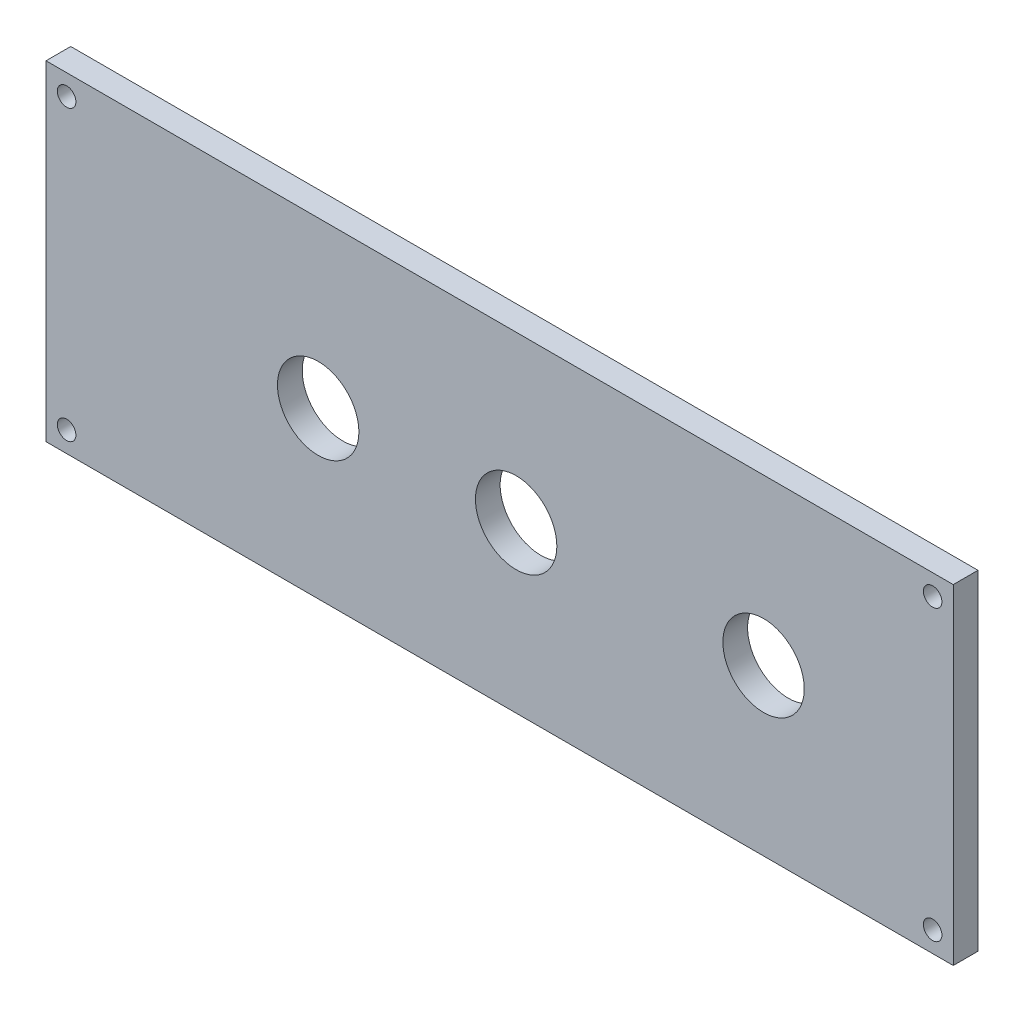
SolidWorks part; units mm, degrees
ref_plane "Front Plane" through (0, 0, 0) normal (0, 0, 1) x (1, 0, 0)
ref_plane "Top Plane" through (0, 0, 0) normal (0, 1, 0) x (1, 0, 0)
ref_plane "Right Plane" through (0, 0, 0) normal (1, 0, 0) x (0, 0, -1)
sketch "Sketch1" plane through (0, 0, 0) normal (0, 0, 1) x (1, 0, 0)
  line L1 (0, 0) -> (110, 0)
  line L2 (0, 0) -> (0, 40)
  line L3 (0, 40) -> (110, 40)
  line L4 (110, 0) -> (110, 40)
  point P6 (108.7458, 40)
  dimension "D1" = 110
  dimension "D2" = 40
extrude "Boss-Extrude1" add sketch "Sketch1" along normal blind 3 contours L3 L4 L1 L2
sketch "Sketch2" plane through (0, 0, 3) normal (0, 0, 1) x (1, 0, 0)
  line L0 (0, 20) -> (110, 20) construction
  line L1 (0, 0) -> (0, 40) construction
  line L2 (110, 0) -> (110, 40) construction
  line L3 (0, 40) -> (110, 40) construction
  line L4 (55, 40) -> (55, 0) construction
  line L5 (0, 0) -> (110, 0) construction
  line L6 (48.175, 16) -> (48.175, 8)
  line L7 (45, 32) -> (48.175, 32)
  line L8 (45, 32) -> (45, 24)
  line L9 (45, 24) -> (48.175, 24)
  line L10 (48.175, 32) -> (48.175, 24)
  line L11 (45, 8) -> (48.175, 8)
  line L12 (45, 16) -> (45, 8)
  line L13 (45, 16) -> (48.175, 16)
  line L14 (48.175, 32) -> (48.175, 16) construction
  line L15 (0, 40) -> (110, 40) construction
  circle A1 centre (33, 20) radius 4.9365
  circle A2 centre (57, 20) radius 4.9365
  circle A3 centre (2.5, 37.5) radius 1.125
  circle A4 centre (107.5, 37.5) radius 1.125
  circle A5 centre (107.5, 2.5) radius 1.125
  circle A6 centre (2.5, 2.5) radius 1.125
  circle A7 centre (87, 20) radius 4.935
  dimension "D1" = 33
  dimension "D2" = 9.873
  dimension "D3" = 9.873
  dimension "D7" = 2.25
  dimension "D15" = 9.87
  dimension "D4" = 3.175
  dimension "D5" = 8
  dimension "D6" = 24
  dimension "D8" = 2.5
  dimension "D9" = 2.5
  dimension "D10" = 12
  dimension "D11" = 16
  dimension "D13" = 16
  dimension "D14" = 30
  dimension "D12" = 2
extrude "Cut-Extrude1" cut sketch "Sketch2" against normal through all contours A3 | A6 | A1 | A2 | A4 | A5 | A7 region at (33, 20, 3) region at (57, 20, 3) region at (2.5, 37.5, 3) region at (107.5, 37.5, 3) region at (107.5, 2.5, 3) region at (2.5, 2.5, 3) region at (87, 20, 3)
